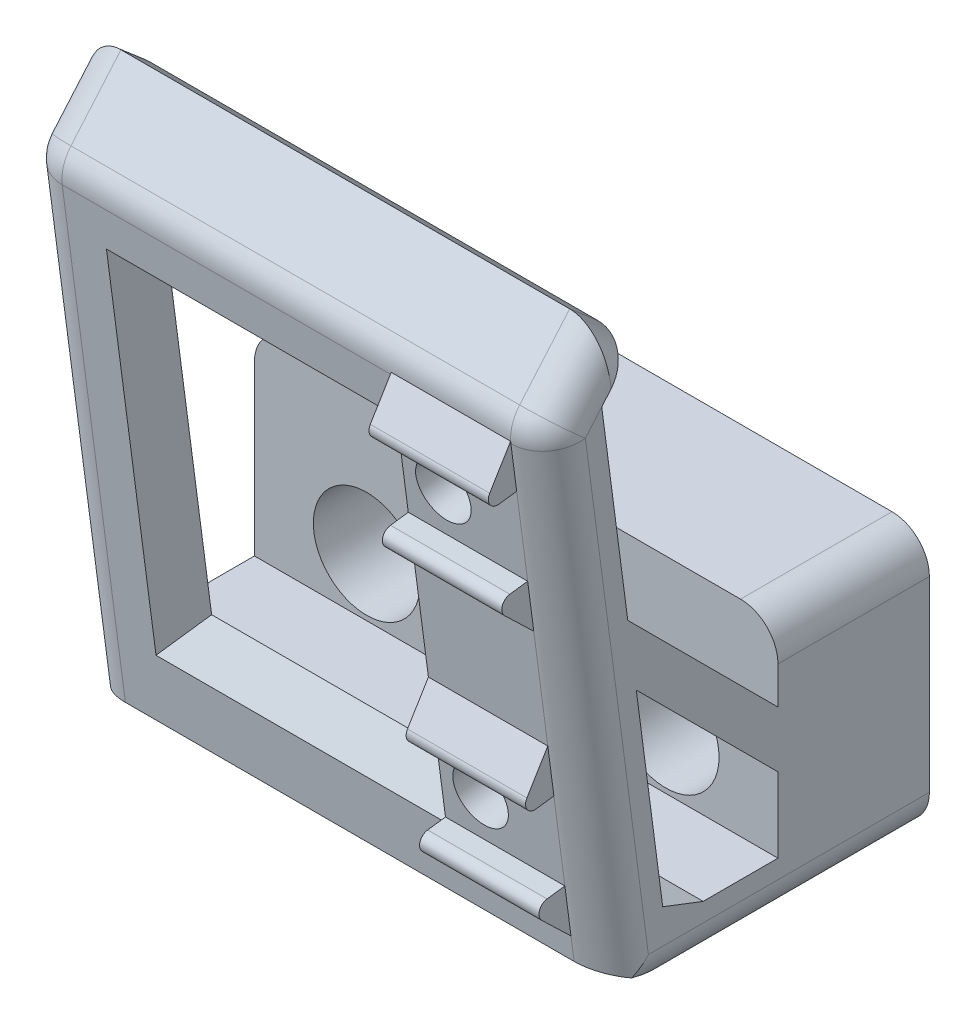
SolidWorks part; units mm, degrees
ref_plane "Front Plane" through (0, 0, 0) normal (0, 0, 1) x (1, 0, 0)
ref_plane "Top Plane" through (0, 0, 0) normal (0, 1, 0) x (1, 0, 0)
ref_plane "Right Plane" through (0, 0, 0) normal (1, 0, 0) x (0, 0, -1)
sketch "Sketch2" plane through (0, 0, 0) normal (0, 0, 1) x (1, 0, 0)
  line L0 (-48.5, -15) -> (-48.5, 24.9) construction
  line L1 (-76.5, -15) -> (-48.5, -15)
  line L2 (-76.5, -15) -> (-76.5, -1)
  line L3 (-76.5, -1) -> (-48.5, -1)
  line L4 (-48.5, -15) -> (-48.5, -1)
  circle A0 centre (-54.5, -8.9) radius 2.85
  circle A1 centre (-70.5, -8.9) radius 2.85
  circle A3 centre (-70.5, -8.9) radius 2.1 construction
  circle A4 centre (-54.5, -8.9) radius 2.1 construction
  dimension "D2" = 5.7
  dimension "D1" = 14
extrude "Boss-Extrude1" add sketch "Sketch2" along normal blind 8.1 from surface at 2
sketch "Sketch6" plane through (-76.5, 0, 0) normal (-1, 0, 0) x (0, 0, 1)
  line L0 (10.1, -15) -> (14.656, -15)
  line L1 (14.656, -15) -> (19.0039, -13.331)
  line L2 (19.0039, -13.331) -> (22.5, 13.2247)
  line L4 (19.5257, 13.6162) -> (16.2625, -11.1699)
  line L5 (16.2625, -11.1699) -> (14.1, -12)
  line L6 (14.1, -12) -> (10.1, -12)
  line L7 (10.1, -12) -> (10.1, -15)
  line L8 (19.5257, 13.6162) -> (17.7237, 15.712)
  line L9 (16.2625, -11.1699) -> (16.2625, 13.6162) construction
  line L10 (24, 1.65) -> (24, 48.05) construction
  line L11 (17.7237, 15.712) -> (19.2402, 17.0159)
  line L12 (19.2402, 17.0159) -> (22.5, 13.2247)
  line L13 (19.5257, 13.6162) -> (22.5, 13.2247) construction
  dimension "D1" = 3
  dimension "D2" = 3
  dimension "D5" = 25
  dimension "D6" = 4
  dimension "D3" = 3
  dimension "D7" = 7.5
  dimension "D8" = 21
  dimension "D4" = 1.5
  dimension "D9" = 2
  dimension "D10" = 5
extrude "Boss-Extrude5" add sketch "Sketch6" against normal up to surface (28 mm away) up to face at (-48.5, -8, 6.05)
sketch "Sketch7" plane through (0, -2.6864, 20.4053) normal (0, -0.1305, 0.9914) x (1, 0, 0)
  line L1 (-72.406, 13.0699) -> (-56.886, 13.0699)
  line L2 (-72.406, 13.0699) -> (-72.406, -7.2501)
  line L3 (-72.406, -7.2501) -> (-56.886, -7.2501)
  line L4 (-52.086, 13.0699) -> (-52.086, -7.2501) construction
  line L6 (-56.886, -7.2501) -> (-56.886, 13.0699)
  line L7 (-56.886, 13.0699) -> (-52.086, 13.0699) construction
  line L8 (-56.886, -7.2501) -> (-52.086, -7.2501) construction
  line L9 (-48.5, 16.0484) -> (-48.5, -10.7365) construction
  line L10 (-54.716, 10.5299) -> (-54.716, -4.7101) construction
  line L11 (-48.5, 16.0484) -> (-76.5, 16.0484) construction
  circle A0 centre (-54.716, -4.7101) radius 1.475
  circle A1 centre (-54.716, 10.5299) radius 1.475
  point P0 (-62.5, 2.6559)
  point P6 (0, 0)
  point P12 (-54.716, 2.9099)
  point P13 (-52.086, 2.9099)
  point P14 (-62.5, 16.0484)
  point P18 (-48.5, 2.6559)
  dimension "D7" = 2.95
  dimension "D1" = 10.414
  dimension "D2" = 9.906
  dimension "D3" = 20.32
  dimension "D4" = 20.32
  dimension "D5" = 4.8
  dimension "D6" = 15.24
  dimension "D8" = 2.63
extrude "Cut-Extrude1" cut sketch "Sketch7" against normal up to next
sketch "Sketch10" plane through (-48.5, 0, 0) normal (1, 0, 0) x (0, 0, -1)
  line L0 (-18.1323, 3.0323) -> (-17.6774, -0.4226)
  line L1 (-19.5257, 13.6162) -> (-16.2625, -11.1699) construction
  line L2 (-17.6774, -0.4226) -> (-10.1, -8)
  line L3 (-10.1, -1) -> (-10.1, -12) construction
  line L4 (-10.1, -8) -> (-10.1, -5)
  line L5 (-10.1, -5) -> (-18.1323, 3.0323)
  point P4 (-10.1, -6.5)
  point P9 (-10.1, -6.5)
  dimension "D1" = 3
  dimension "D2" = 45
extrude "Boss-Extrude7" add sketch "Sketch10" against normal blind 2
fillet "Fillet1" radius 2 11 edges at (-76.5, -15, 8.328) (-48.5, -15, 8.328) (-76.5, -1, 6.05) (-48.5, -1, 6.05) (-48.5, 15.1203, 20.8701) (-76.5, 15.1203, 20.8701) (-48.5, -0.0532, 20.7519) (-76.5, -0.0532, 20.7519) (-62.5, 13.2247, 22.5) (-48.5, 16.3639, 18.4819) (-76.5, 16.3639, 18.4819)
sketch "Sketch11" plane through (-48.5, 0, 0) normal (1, 0, 0) x (0, 0, -1)
  line L0 (-21.1597, 3.0441) -> (-23.4689, 5.2617)
  line L1 (-19.0475, -13) -> (-22.5, 13.2247) construction
  line L2 (-23.4689, 5.2617) -> (-21.486, 5.5227)
  line L3 (-21.486, 5.5227) -> (-21.1597, 3.0441)
  line L4 (-22.3997, 12.4628) -> (-22.0734, 9.9842)
  line L6 (-22.0734, 9.9842) -> (-24.0563, 9.7232)
  line L7 (-24.0563, 9.7232) -> (-22.3997, 12.4628)
  line L8 (-23.8879, 8.4442) -> (-23.6373, 6.5406) construction
  line L9 (-21.4797, -9.848) -> (-19.4968, -9.5869)
  line L10 (-19.4968, -9.5869) -> (-19.1705, -12.0655)
  line L11 (-19.1705, -12.0655) -> (-21.4797, -9.848)
  line L12 (-22.0671, -5.3865) -> (-20.0842, -5.1254)
  line L13 (-20.0842, -5.1254) -> (-20.4105, -2.6468)
  line L14 (-20.4105, -2.6468) -> (-22.0671, -5.3865)
  line L15 (-24.0563, 9.7232) -> (-23.4689, 5.2617) construction
  line L16 (-23.8879, 8.4442) -> (-23.6373, 6.5406) construction
  line L17 (-22.0671, -5.3865) -> (-21.4797, -9.848) construction
  line L18 (-21.8987, -6.6654) -> (-21.6481, -8.569) construction
  line L19 (-21.8987, -6.6654) -> (-21.6481, -8.569) construction
  line L20 (-19.0039, -13.331) -> (-22.3833, 12.3379) construction
  point P18 (-23.7626, 7.4924)
  point P19 (-23.7626, 7.4924)
  point P20 (-22.6438, -4.7817)
  point P23 (-21.7734, -7.6172)
  point P24 (-21.7734, -7.6172)
  point P25 (0, 0)
  point P28 (0, 0)
  point P29 (0, 0)
  dimension "D1" = 4.5
  dimension "D2" = 2.5
extrude "Boss-Extrude8" add sketch "Sketch11" against normal up to surface (6.386 mm away) from vertex at -2 up to face at (-56.886, 0.3944, 19.2979) starting at point (-50.5, 12.3379, 22.3833)
fillet "Fillet2" radius 0.5 4 edges at (-53.693, 9.7232, 24.0563) (-53.693, 5.2617, 23.4689) (-53.693, -5.3865, 22.0671) (-53.693, -9.848, 21.4797)
equation "\"D2@Sketch6\"=\"D1@Sketch6\""
equation "\"width\"= 24"
equation "\"thk\"= 3"
equation "\"holesize\"= 4.2"
equation "\"holedistance\"= ( 20 + 12 ) / 2"
equation "\"threaded_hole\"= 3.9"
equation "\"fillet_radius\"= 2"
equation "\"ground_clearance\"= 25"
equation "\"tire_thk\"= 3"
equation "\"innerwheel_diam\" = \"wheel_diam\"-2*\"tire_thk\""
equation "\"innerwheel_thk\"= 8"
equation "\"wheel_diam\"= 2*(\"width\"/2+\"ground_clearance\")"
equation "\"coloursensor_holesize\"= 2.65"
equation "\"hole_to_edge\" = 4"
equation "\"D7@Sketch7\"=\"coloursensor_holesize\"+0.3"
equation "\"M4_insert_diam\"= 5.7"
equation "\"D2@Sketch2\"=\"M4_insert_diam\""
